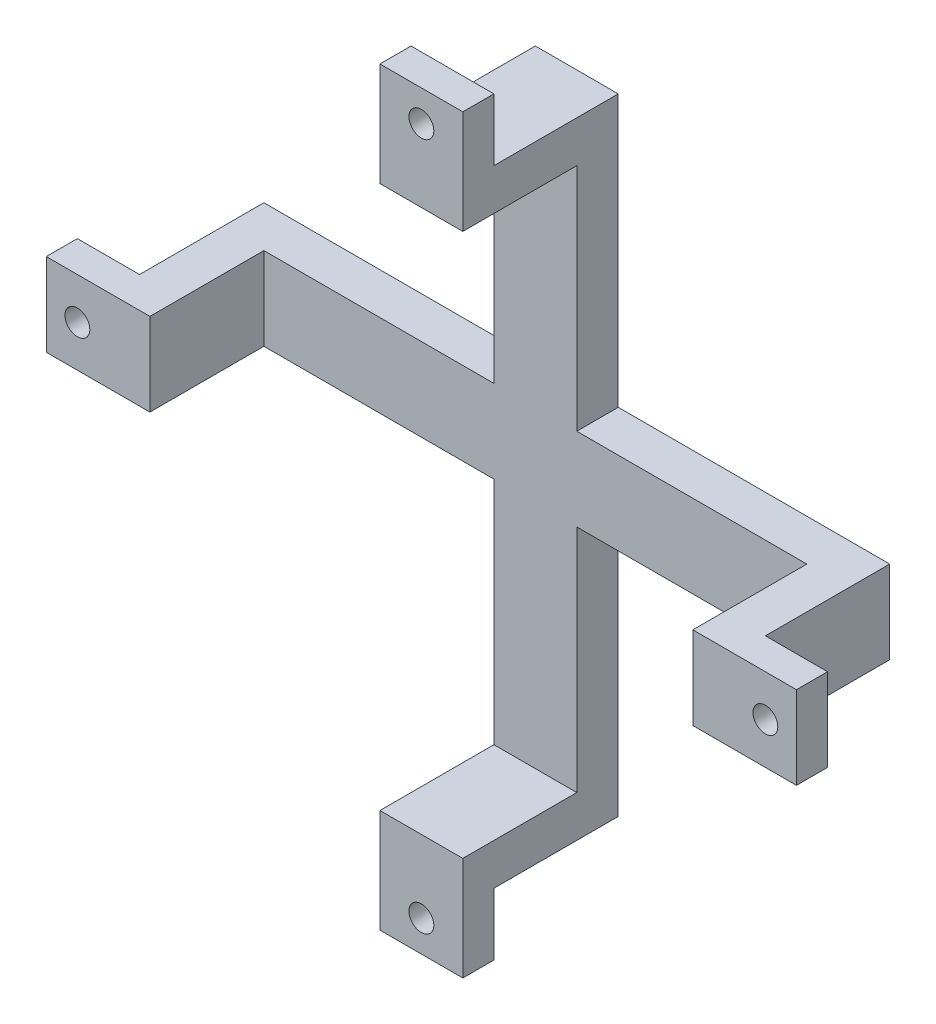
SolidWorks part; units mm, degrees
ref_plane "前视基准面" through (0, 0, 0) normal (0, 0, 1) x (1, 0, 0)
ref_plane "上视基准面" through (0, 0, 0) normal (0, 1, 0) x (1, 0, 0)
ref_plane "右视基准面" through (0, 0, 0) normal (1, 0, 0) x (0, 0, -1)
other "Configuration Table"
sketch "草图1" plane through (0, 0, 0) normal (0, 0, 1) x (1, 0, 0)
  line L1 (-13.1, 2) -> (13.1, 2)
  line L2 (-13.1, 2) -> (-13.1, -2)
  line L3 (-13.1, -2) -> (13.1, -2)
  line L4 (13.1, 2) -> (13.1, -2)
  line L5 (-2, 13.1) -> (2, 13.1)
  line L6 (-2, 13.1) -> (-2, -13.1)
  line L7 (-2, -13.1) -> (2, -13.1)
  line L8 (2, 13.1) -> (2, -13.1)
  line L9 (-2, 13.1) -> (2, 13.1)
  line L10 (-2, 13.1) -> (-2, 15.1)
  line L11 (-2, 15.1) -> (2, 15.1)
  line L12 (2, 13.1) -> (2, 15.1)
  line L13 (13.1, 2) -> (15.1, 2)
  line L14 (13.1, 2) -> (13.1, -2)
  line L15 (13.1, -2) -> (15.1, -2)
  line L16 (15.1, 2) -> (15.1, -2)
  line L17 (2, -13.1) -> (-2, -13.1)
  line L18 (2, -13.1) -> (2, -15.1)
  line L19 (2, -15.1) -> (-2, -15.1)
  line L20 (-2, -13.1) -> (-2, -15.1)
  line L21 (-13.1, -2) -> (-15.1, -2)
  line L22 (-13.1, -2) -> (-13.1, 2)
  line L23 (-13.1, 2) -> (-15.1, 2)
  line L24 (-15.1, -2) -> (-15.1, 2)
  line L25 (-2, 15.1) -> (2, 15.1)
  line L26 (-2, 15.1) -> (-2, 18.1)
  line L27 (-2, 18.1) -> (2, 18.1)
  line L28 (2, 15.1) -> (2, 18.1)
  line L29 (15.1, 2) -> (18.1, 2)
  line L30 (15.1, 2) -> (15.1, -2)
  line L31 (15.1, -2) -> (18.1, -2)
  line L32 (18.1, 2) -> (18.1, -2)
  line L33 (2, -15.1) -> (-2, -15.1)
  line L34 (2, -15.1) -> (2, -18.1)
  line L35 (2, -18.1) -> (-2, -18.1)
  line L36 (-2, -15.1) -> (-2, -18.1)
  line L37 (-15.1, -2) -> (-18.1, -2)
  line L38 (-15.1, -2) -> (-15.1, 2)
  line L39 (-15.1, 2) -> (-18.1, 2)
  line L40 (-18.1, -2) -> (-18.1, 2)
  circle A3 centre (-16.6, 0) radius 0.6
  circle A4 centre (16.6, 0) radius 0.6
  circle A5 centre (0, -16.6) radius 0.6
  circle A6 centre (0, 16.6) radius 0.6
  point P4 (-2, 0)
  point P6 (13.1, 0)
  point P7 (0, 2)
  point P12 (0, -13.1)
  point P38 (0, 0)
  point P39 (0, 0)
  point P40 (0, 0)
  point P41 (-16.6, 2)
  point P42 (0, 0)
  point P43 (16.6, 2)
  point P44 (0, 0)
  point P45 (-2, 16.6)
  point P46 (0, 0)
  point P47 (-2, -16.6)
  dimension "D4" = 3
  dimension "D1" = 4
  dimension "D2" = 26.2
  dimension "D5" = 1.2
  dimension "D3" = 2
extrude "凸台-拉伸1" add sketch "草图1" along normal blind 2 contours L3 L4 L1 L2 | L7 L8 L5 L6
extrude "凸台-拉伸2" add sketch "草图1<6>" along normal blind 7.5 contours L16 L13 L4 L15 | L5 L12 L11 L10 | L7 L20 L19 L18 | L24 L21 L2 L23 region at (-14.1, 0, 0) region at (0, 14.1, 0) region at (14.1, 0, 0) region at (0, -14.1, 0)
sketch "草图1<6>" plane through (0, 0, 0) normal (0, 0, 1) x (1, 0, 0) same geometry as "草图1"
extrude "凸台-拉伸3" add sketch "草图1<7>" against normal blind 1.5 from surface contours L40 L37 L24 L39 | L19 L36 L35 L34 | L32 L29 L16 L31 | L11 L28 L27 L26 region at (-15.15, 0, 0) region at (-1.95, 16.6, 0) region at (16.6, 1.95, 0) region at (0, -15.15, 0) starting at face at (-14.1, 0, 7.5)
sketch "草图1<7>" plane through (0, 0, 0) normal (0, 0, 1) x (1, 0, 0) same geometry as "草图1"
